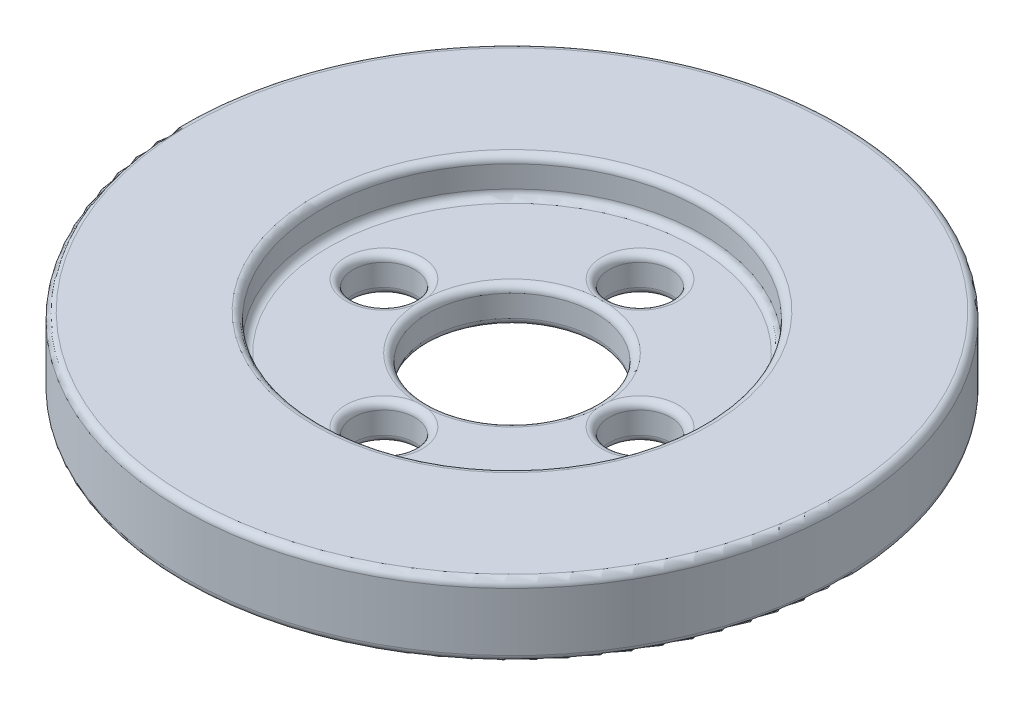
SolidWorks part; units mm, degrees
note: The reader was unsure of these and kept them because the rebuilt part matched: shared geometry of "Sketch1<3>".
ref_plane "Front Plane" through (0, 0, 0) normal (0, 0, 1) x (1, 0, 0)
ref_plane "Top Plane" through (0, 0, 0) normal (0, 1, 0) x (1, 0, 0)
ref_plane "Right Plane" through (0, 0, 0) normal (1, 0, 0) x (0, 0, -1)
sketch "Sketch1" plane through (0, 0, 0) normal (0, 1, 0) x (1, 0, 0)
  circle A0 centre (0, 0) radius 18.15
  circle A1 centre (0, 0) radius 10.5
  dimension "D1" = 21
  dimension "D2" = 36.3
extrude "Boss-Extrude1" add sketch "Sketch1" along normal blind 2
extrude "Boss-Extrude2" add sketch "Sketch1<3>" against normal blind 2 contours A1 | A0 A1
sketch "Sketch1<3>" plane through (0, 0, 0) normal (0, 1, 0) x (1, 0, 0) same geometry as "Sketch1"
sketch "Sketch2" plane through (0, 0, 0) normal (0, 1, 0) x (1, 0, 0)
  line L0 (0, 0) -> (0, 7.05) construction
  circle A0 centre (0, 0) radius 4.6
  circle A1 centre (0, 7.05) radius 1.7
  circle A2 centre (7.05, 0) radius 1.7
  circle A3 centre (0, -7.05) radius 1.7
  circle A4 centre (-7.05, 0) radius 1.7
  point P5 (7.8761, 2.0646)
  point P6 (0, 0)
  point P14 (0, 0)
  dimension "D1" = 9.2
  dimension "D2" = 3.4
  dimension "D3" = 7.05
  dimension "D4" = 4
extrude "Cut-Extrude1" cut sketch "Sketch2" against normal blind 2
fillet "Fillet1" radius 0.4 14 edges at (0, 0, 10.5) (-7.05, 0, 1.7) (0, 0, 8.75) (7.05, 0, 1.7) (0, 0, -5.35) (0, 0, 4.6) (0, -2, 18.15) (0, -2, 4.6) (-7.05, -2, 1.7) (0, -2, 8.75) (7.05, -2, 1.7) (0, -2, -5.35) (0, 2, 10.5) (0, 2, 18.15)
